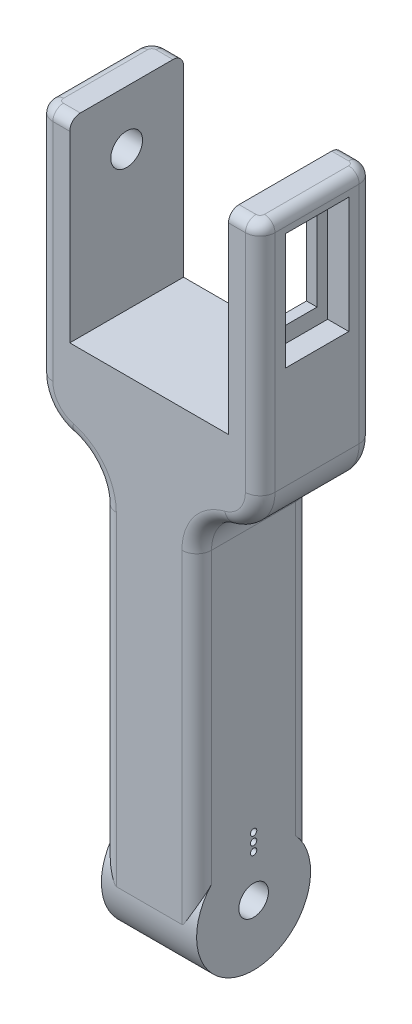
SolidWorks part; units mm, degrees
ref_plane "Front Plane" through (0, 0, 0) normal (0, 0, 1) x (1, 0, 0)
ref_plane "Top Plane" through (0, 0, 0) normal (0, 1, 0) x (1, 0, 0)
ref_plane "Right Plane" through (0, 0, 0) normal (1, 0, 0) x (0, 0, -1)
sketch "Sketch1" plane through (0, 0, 0) normal (1, 0, 0) x (0, 0, -1)
  line L2 (-26.8892, 105.7962) -> (-26.8892, -105.7962)
  line L4 (26.8892, 105.7962) -> (26.8892, -105.7962)
  line L5 (-26.8892, 105.7962) -> (26.8892, -105.7962) construction
  line L6 (-26.8892, -105.7962) -> (26.8892, 105.7962) construction
  arc A0 (-26.8892, -105.7962) -> (26.8892, -105.7962) centre (0, -107.5069) ccw
  arc A1 (26.8892, 105.7962) -> (-26.8892, 105.7962) centre (0, 92.4931) ccw
  point P0 (0, 0)
  dimension "D2" = 30
  dimension "D1" = 200
extrude "Boss-Extrude1" add sketch "Sketch1" along normal blind 45
sketch "Sketch4" plane through (0, 0, 0) normal (-1, 0, 0) x (0, 0, 1)
  circle A0 centre (0, -105.5304) radius 15
  arc A1 (-26.8892, -105.7962) -> (26.8892, -105.7962) centre (0, -107.5069) ccw construction
  point P7 (0, -134.4504)
  dimension "D2" = 30
  dimension "D1" = 28.92
extrude "Cut-Extrude1" cut sketch "Sketch4" against normal blind 12
sketch "Sketch5" plane through (45, 0, 0) normal (1, 0, 0) x (0, 0, -1)
  circle A0 centre (0, -105.7962) radius 7.002
  circle A1 centre (0, -85.9562) radius 1.5
  circle A2 centre (0, -81.9562) radius 1.5
  circle A3 centre (0, -77.9562) radius 1.5
  dimension "D3" = 3
  dimension "D4" = 3
  dimension "D6" = 3
  dimension "D1" = 19.84
  dimension "D2" = 4
  dimension "D5" = 4
extrude "Cut-Extrude2" cut sketch "Sketch5" against normal blind 13
sketch "Sketch6" plane through (0, 0, -26.8892) normal (0, 0, -1) x (-1, 0, 0)
  line L0 (0, -105.7962) -> (0, 105.7962) construction
  line L1 (0, 67.3962) -> (0, -61.8065)
  line L2 (-22.5, 105.7962) -> (-22.5, 44.3596) construction
  line L3 (-45, 105.7962) -> (0, 105.7962) construction
  line L4 (-45, 67.3962) -> (-45, -61.8065)
  arc A0 (0, 67.3962) -> (0, -61.8065) centre (125.5181, 2.7948) ccw
  arc A1 (-45, 67.3962) -> (-45, -61.8065) centre (-170.5181, 2.7948) cw
extrude "Cut-Extrude3" cut sketch "Sketch6" against normal blind 73
sketch "Sketch7" plane through (0, 0, 0) normal (-1, 0, 0) x (0, 0, 1)
  line L1 (-26.8892, 105.7962) -> (31.4821, 105.7962)
  line L2 (-26.8892, 105.7962) -> (-26.8892, 127.1384)
  line L3 (-26.8892, 127.1384) -> (31.4821, 127.1384)
  line L4 (31.4821, 105.7962) -> (31.4821, 127.1384)
extrude "Cut-Extrude4" cut sketch "Sketch7" against normal blind 53
sketch "Sketch14" plane through (0, 0, -26.8892) normal (0, 0, -1) x (-1, 0, 0)
  line L0 (0, 105.7962) -> (15, 105.7962)
  line L1 (15, 105.7962) -> (15, 197.3962)
  line L2 (15, 197.3962) -> (30, 197.3962)
  line L3 (30, 197.3962) -> (30, 67.3962)
  line L4 (30, 67.3962) -> (0, 67.3962)
  line L5 (0, 67.3962) -> (0, 105.7962)
  line L6 (-22.5, 105.7962) -> (-22.5, 213.7939) construction
  line L7 (-45, 105.7962) -> (0, 105.7962) construction
  line L8 (-75, 67.3962) -> (-45, 67.3962)
  line L9 (-75, 197.3962) -> (-75, 67.3962)
  line L10 (-60, 197.3962) -> (-75, 197.3962)
  line L11 (-60, 105.7962) -> (-60, 197.3962)
  line L12 (-45, 105.7962) -> (-60, 105.7962)
  line L13 (-45, 67.3962) -> (-45, 105.7962)
  dimension "D1" = 130
  dimension "D2" = 15
  dimension "D3" = 30
extrude "Boss-Extrude6" add sketch "Sketch14" against normal up to surface (53.7784 mm away) up to face at (22.5, 1.3974, 26.8892)
sketch "Sketch15" plane through (75, 0, 0) normal (1, 0, 0) x (0, 0, -1)
  line L1 (-15, 189.5067) -> (15, 189.5067)
  line L2 (-15, 189.5067) -> (-15, 134.5067)
  line L3 (-15, 134.5067) -> (15, 134.5067)
  line L4 (15, 189.5067) -> (15, 134.5067)
  line L5 (-15, 189.5067) -> (15, 134.5067) construction
  line L6 (-15, 134.5067) -> (15, 189.5067) construction
  point P0 (0, 162.0067)
  dimension "D1" = 30
  dimension "D2" = 55
extrude "Cut-Extrude7" cut sketch "Sketch15" against normal blind 10
sketch "Sketch16" plane through (65, 0, 0) normal (1, 0, 0) x (0, 0, -1)
  line L0 (15, 189.5067) -> (-15, 189.5067) construction
  line L1 (-10, 182.0067) -> (10, 182.0067)
  line L2 (-10, 182.0067) -> (-10, 142.0067)
  line L3 (-10, 142.0067) -> (10, 142.0067)
  line L4 (10, 182.0067) -> (10, 142.0067)
  line L5 (-10, 182.0067) -> (10, 142.0067) construction
  line L6 (-10, 142.0067) -> (10, 182.0067) construction
  point P0 (0, 162.0067)
  dimension "D1" = 20
  dimension "D2" = 40
  dimension "D3" = 7.5
extrude "Cut-Extrude8" cut sketch "Sketch16" against normal blind 10
sketch "Sketch17" plane through (-30, 0, 0) normal (-1, 0, 0) x (0, 0, 1)
  line L0 (26.8892, 197.3962) -> (26.8892, 67.3962) construction
  line L1 (26.8892, 197.3962) -> (-26.8892, 197.3962) construction
  circle A0 centre (0, 171.6262) radius 7.5
  dimension "D1" = 15
  dimension "D2" = 26.8892
  dimension "D3" = 25.77
extrude "Cut-Extrude9" cut sketch "Sketch17" against normal blind 24
sketch "Sketch18" plane through (0, 0, 26.8892) normal (0, 0, 1) x (1, 0, 0)
  line L1 (0, 67.3962) -> (45, 67.3962)
  line L2 (0, 67.3962) -> (0, -61.8065)
  line L3 (0, -61.8065) -> (45, -61.8065)
  line L4 (45, 67.3962) -> (45, -61.8065)
extrude "Boss-Extrude7" add sketch "Sketch18" against normal up to surface (53.7784 mm away) up to face at (22.5, 66.8254, -26.8892)
fillet "Fillet1" radius 20 2 edges at (45, 67.3962, 0) (0, 67.3962, 0)
fillet "Fillet2" radius 20 2 edges at (75, 67.3962, 0) (-30, 67.3962, 0)
fillet "Fillet3" radius 7 16 edges at (75, 141.7611, -26.8892) (70.8114, 73.8785, -26.8892) (49.1886, 59.6436, -26.8892) (-30, 141.7611, -26.8892) (-25.8114, 73.8785, -26.8892) (-4.1886, 59.6436, -26.8892) (75, 141.7611, 26.8892) (70.8114, 73.8785, 26.8892) (49.1886, 59.6436, 26.8892) (-30, 141.7611, 26.8892) (-25.8114, 73.8785, 26.8892) (-4.1886, 59.6436, 26.8892) (45, -29.2, -26.8892) (0, -29.2, -26.8892) (45, -29.2, 26.8892) (0, -29.2, 26.8892)
fillet "Fillet4" radius 5 10 edges at (64, 197.3962, 26.8892) (72.9497, 197.3962, 24.8389) (64, 197.3962, -26.8892) (72.9497, 197.3962, -24.8389) (-19, 197.3962, 26.8892) (-27.9497, 197.3962, 24.8389) (-19, 197.3962, -26.8892) (-27.9497, 197.3962, -24.8389) (75, 197.3962, 0) (-30, 197.3962, 0)
